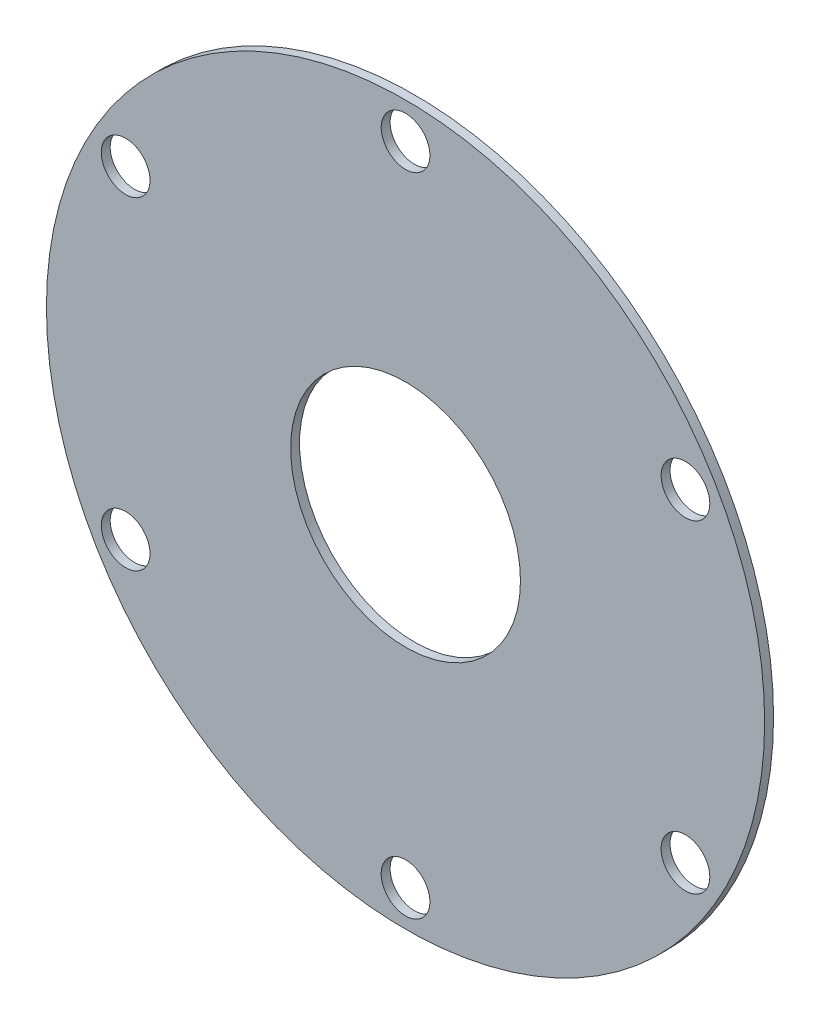
SolidWorks part; units mm, degrees
material "6061-T6 (SS)"
ref_plane "Front Plane" through (0, 0, 0) normal (0, 0, 1) x (1, 0, 0)
ref_plane "Top Plane" through (0, 0, 0) normal (0, 1, 0) x (1, 0, 0)
ref_plane "Right Plane" through (0, 0, 0) normal (1, 0, 0) x (0, 0, -1)
sketch "Sketch1" plane through (0, 0, 0) normal (0, 0, 1) x (1, 0, 0)
  circle A0 centre (0, 0) radius 31.75
  circle A1 centre (0, 0) radius 10.16
  dimension "D1" = 63.5
  dimension "D2" = 20.32
extrude "Boss-Extrude1" add sketch "Sketch1" along normal blind 0.7874
hole_wizard "#8 Clearance Hole1" positions "Sketch3" profile "Sketch4" hole size "#8" standard "Ansi Inch" end condition through all
sketch "Sketch3" plane through (0, 0, 0.7874) normal (0, 0, 1) x (1, 0, 0)
  point P0 (0, 28.575)
  point P10 (24.7467, 14.2875)
  point P11 (24.7467, -14.2875)
  point P12 (0, -28.575)
  point P13 (-24.7467, -14.2875)
  point P14 (-24.7467, 14.2875)
  dimension "D1" = 28.575
sketch "Sketch4" plane through (0, 28.575, 0.7874) normal (1, 0, 0) x (0, -1, 0)
  line L0 (0, 0) -> (0, 0.7874)
  line L1 (0, 0.7874) -> (2.1526, 0.7874)
  line L2 (2.1526, 0.7874) -> (2.1526, 0)
  line L5 (2.1526, 0) -> (0, 0)
  line L11 (0, -6.35) -> (0, 107.95) construction
  dimension "Thru Hole Dia." = 4.3053
  dimension "Thru Hole Depth" = 0.7874
